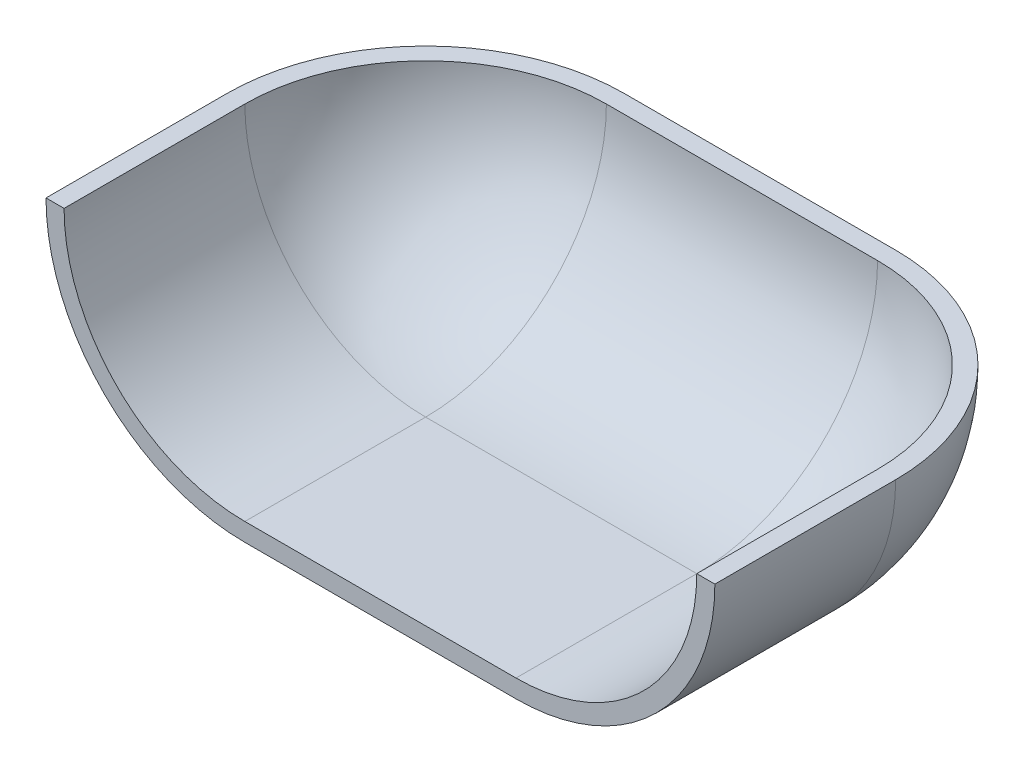
SolidWorks part; units mm, degrees
note: The reader was unsure of these and kept them because the rebuilt part matched: shared geometry of "Sketch1<2>".
material "PE High Density"
ref_plane "Front" through (0, 0, 0) normal (0, 0, 1) x (1, 0, 0)
ref_plane "Top" through (0, 0, 0) normal (0, 1, 0) x (1, 0, 0)
ref_plane "Right" through (0, 0, 0) normal (1, 0, 0) x (0, 0, -1)
sketch "Sketch1" plane through (0, 0, 0) normal (0, 0, 1) x (1, 0, 0)
  line L0 (0, 0) -> (19.05, 0)
  line L1 (9.525, -5.9485) -> (9.525, 12.7) construction
  line L2 (-12.7, 12.7) -> (9.525, 12.7) construction
  arc A0 (0, 0) -> (-12.7, 12.7) centre (0, 12.7) cw
  arc A1 (19.05, 0) -> (31.75, 12.7) centre (19.05, 12.7) ccw
  point P12 (9.525, 0)
  dimension "D2" = 12.7
  dimension "D1" = 9.525
revolve "Revolve-Thin1" add sketch "Sketch1" angle 90 about L2
extrude "Extrude-Thin1" add sketch "Sketch1<2>" along normal blind 12.7 thin
sketch "Sketch1<2>" plane through (0, 0, 0) normal (0, 0, 1) x (1, 0, 0) same geometry as "Sketch1"
